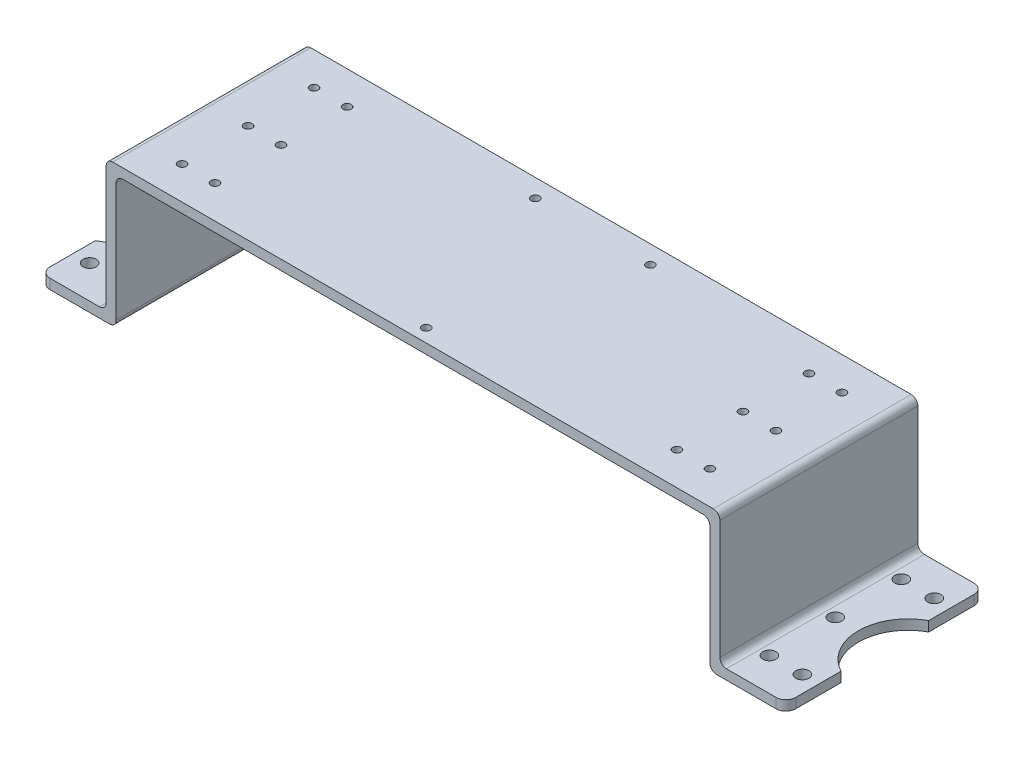
SolidWorks part; units mm, degrees
ref_plane "Front" through (0, 0, 0) normal (0, 0, 1) x (1, 0, 0)
ref_plane "Top" through (0, 0, 0) normal (0, 1, 0) x (1, 0, 0)
ref_plane "Right" through (0, 0, 0) normal (1, 0, 0) x (0, 0, -1)
sketch "草图1" plane through (0, 0, 0) normal (0, 1, 0) x (1, 0, 0)
  line L1 (-93, 30) -> (93, 30)
  line L2 (-93, 30) -> (-93, -30)
  line L3 (-93, -30) -> (93, -30)
  line L4 (93, 30) -> (93, -30)
  line L5 (-93, 30) -> (93, -30) construction
  line L6 (-93, -30) -> (93, 30) construction
  point P0 (0, 0)
  dimension "D1" = 186
  dimension "D2" = 60
extrude "凸台-拉伸1" add sketch "草图1" along normal blind 3 contours L3 L4 L1 L2
sketch "草图2" plane through (0, 0, 0) normal (0, -1, 0) x (1, 0, 0)
  line L0 (-93, -30) -> (93, -30) construction
  line L1 (-93, 30) -> (-90, 30)
  line L2 (-93, 30) -> (-93, -30)
  line L3 (-93, -30) -> (-90, -30)
  line L4 (-90, 30) -> (-90, -30)
  dimension "D1" = 3
extrude "凸台-拉伸2" add sketch "草图2" along normal blind 40
sketch "草图3" plane through (-93, 0, 0) normal (-1, 0, 0) x (0, 0, 1)
  line L0 (30, 3) -> (30, -40) construction
  line L1 (-30, -40) -> (30, -40)
  line L2 (-30, -40) -> (-30, -37)
  line L3 (-30, -37) -> (30, -37)
  line L4 (30, -40) -> (30, -37)
  dimension "D1" = 3
extrude "凸台-拉伸3" add sketch "草图3" along normal blind 20 contours L3 L4 L1 L2
sketch "草图4" plane through (0, -37, 0) normal (0, 1, 0) x (1, 0, 0)
  line L0 (0, -65.2575) -> (0, 64.6093) construction
  line L1 (-113, -30) -> (-93, -30) construction
  circle A0 centre (-98, -20) radius 2
  dimension "D1" = 98
  dimension "D3" = 4
  dimension "D2" = 10
extrude "切除-拉伸1" cut sketch "草图4" against normal through all
pattern_linear "阵列(线性)1" count 3 spacing 20 along (0, 0, -1) count 2 spacing 10 along (-1, 0, 0) of "切除-拉伸1"
mirror "镜向4" about plane through (0, 0, 0) normal (1, 0, 0) of "阵列(线性)1", "凸台-拉伸3", "凸台-拉伸2"
sketch "草图5" plane through (0, 3, 0) normal (0, 1, 0) x (1, 0, 0)
  line L0 (-93, -30) -> (93, -30) construction
  circle A0 centre (0, -26) radius 1
  dimension "D1" = 2
  dimension "D2" = 4
extrude "切除-拉伸2" cut sketch "草图5" against normal blind 3
sketch "草图6" plane through (0, 3, 0) normal (0, 1, 0) x (1, 0, 0)
  circle A0 centre (-17.45, 24.5) radius 1
  circle A1 centre (0, -26) radius 1 construction
  dimension "D1" = 2
  dimension "D2" = 50.5
  dimension "D3" = 17.45
extrude "切除-拉伸3" cut sketch "草图6" against normal blind 3 contours A0
mirror "镜向5" about plane through (0, 0, 0) normal (1, 0, 0) of "切除-拉伸3"
sketch "草图7" plane through (0, 3, 0) normal (0, 1, 0) x (1, 0, 0)
  line L0 (-93, -30) -> (93, -30) construction
  line L1 (0, -50) -> (0, 50) construction
  circle A0 centre (-70, -20) radius 1
  dimension "D1" = 2
  dimension "D2" = 10
  dimension "D3" = 70
extrude "切除-拉伸4" cut sketch "草图7" against normal blind 3
pattern_linear "阵列(线性)2" count 3 spacing 20 along (0, 0, -1) count 2 spacing 10 along (-1, 0, 0) of "切除-拉伸4"
mirror "镜向6" about plane through (0, 0, 0) normal (1, 0, 0) of "阵列(线性)2"
hole_wizard "M3 螺纹孔1" positions "草图8" profile "草图9" tap size "M3" standard "GB" end condition through all
sketch "草图8" plane through (0, 3, 0) normal (0, 1, 0) x (1, 0, 0)
  point P0 (-80, -20)
  point P3 (-70, -20)
  point P6 (-70, 0)
  point P9 (-80, 0)
  point P12 (-70, 20)
  point P15 (-80, 20)
  point P18 (70, -20)
  point P21 (80, -20)
  point P24 (70, 0)
  point P27 (80, 0)
  point P30 (70, 20)
  point P33 (80, 20)
sketch "草图9" plane through (-80, 3, 20) normal (1, 0, 0) x (0, 0, 1)
  line L0 (0, 0) -> (0, 43)
  line L1 (0, 43) -> (1.25, 43)
  line L2 (1.25, 43) -> (1.25, 0)
  line L5 (1.25, 0) -> (0, 0)
  line L11 (0, -6.35) -> (0, 107.95) construction
  dimension "通孔螺纹孔钻头直径" = 2.5
  dimension "通孔螺纹孔钻头深度" = 43
cosmetic thread "孔螺蚊线1" parameters "D2"=3
cosmetic thread "孔螺蚊线2" parameters "D2"=3
cosmetic thread "孔螺蚊线3" parameters "D2"=3
cosmetic thread "孔螺蚊线4" parameters "D2"=3
cosmetic thread "孔螺蚊线5" parameters "D2"=3
cosmetic thread "孔螺蚊线6" parameters "D2"=3
cosmetic thread "孔螺蚊线7" parameters "D2"=3
cosmetic thread "孔螺蚊线8" parameters "D2"=3
cosmetic thread "孔螺蚊线9" parameters "D2"=3
cosmetic thread "孔螺蚊线10" parameters "D2"=3
cosmetic thread "孔螺蚊线11" parameters "D2"=3
cosmetic thread "孔螺蚊线12" parameters "D2"=3
hole_wizard "M3 螺纹孔2" positions "草图10" profile "草图11" tap size "M3" standard "GB" end condition through all
sketch "草图10" plane through (0, 3, 0) normal (0, 1, 0) x (1, 0, 0)
  point P0 (-17.45, 24.5)
  point P3 (17.45, 24.5)
  point P6 (0, -26)
sketch "草图11" plane through (-17.45, 3, -24.5) normal (1, 0, 0) x (0, 0, 1)
  line L0 (0, 0) -> (0, 43)
  line L1 (0, 43) -> (1.25, 43)
  line L2 (1.25, 43) -> (1.25, 0)
  line L5 (1.25, 0) -> (0, 0)
  line L11 (0, -6.35) -> (0, 107.95) construction
  dimension "通孔螺纹孔钻头直径" = 2.5
  dimension "通孔螺纹孔钻头深度" = 43
cosmetic thread "孔螺蚊线13" parameters "D2"=3
cosmetic thread "孔螺蚊线14" parameters "D2"=3
cosmetic thread "孔螺蚊线15" parameters "D2"=3
sketch "草图12" plane through (0, -37, 0) normal (0, 1, 0) x (1, 0, 0)
  line L0 (-108, 0) -> (-120, 0) construction
  circle A0 centre (-120, 0) radius 15
  dimension "D1" = 30
  dimension "D2" = 12
extrude "切除-拉伸5" cut sketch "草图12" against normal through all
mirror "镜向7" about plane through (0, 0, 0) normal (1, 0, 0) of "切除-拉伸5"
fillet "圆角2" radius 2 2 edges at (-90, 0, 0) (-93, 3, 0)
fillet "圆角3" radius 2 2 edges at (90, 0, 0) (93, 3, 0)
fillet "圆角4" radius 2 4 edges at (-90, -40, 0) (-93, -37, 0) (93, -37, 0) (90, -40, 0)
fillet "圆角5" radius 3 4 edges at (-113, -38.5, 30) (-113, -38.5, -30) (113, -38.5, -30) (113, -38.5, 30)
